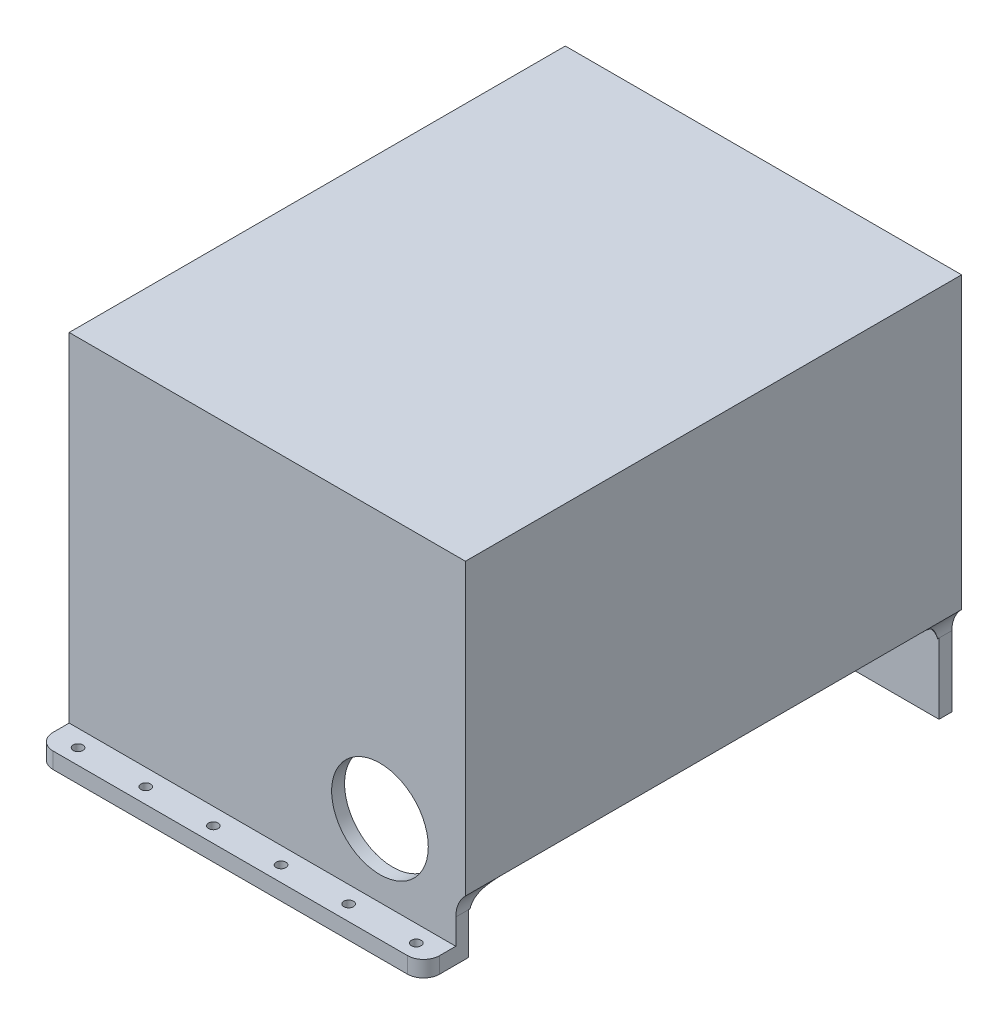
SolidWorks part; units mm, degrees
ref_plane "正面" through (0, 0, 0) normal (0, 0, 1) x (1, 0, 0)
ref_plane "平面" through (0, 0, 0) normal (0, 1, 0) x (1, 0, 0)
ref_plane "右側面" through (0, 0, 0) normal (1, 0, 0) x (0, 0, -1)
sketch "ｽｹｯﾁ1" plane through (0, 0, 0) normal (0, 1, 0) x (1, 0, 0)
  line L1 (0, 0) -> (120, 0)
  line L2 (0, 0) -> (0, 10)
  line L3 (0, 10) -> (120, 10)
  line L4 (120, 0) -> (120, 10)
  circle A0 centre (8, 4.759) radius 1.5
  circle A1 centre (29, 4.759) radius 1.5
  circle A2 centre (50, 4.759) radius 1.5
  circle A3 centre (71, 4.759) radius 1.5
  circle A4 centre (92, 4.759) radius 1.5
  circle A5 centre (113, 4.759) radius 1.5
  dimension "D2" = 3
  dimension "D3" = 3
  dimension "D4" = 3
  dimension "D5" = 3
  dimension "D9" = 3
  dimension "D11" = 3
  dimension "D12" = 21
  dimension "D1" = 10
  dimension "D6" = 21
  dimension "D7" = 21
  dimension "D8" = 21
  dimension "D10" = 21
  dimension "D13" = 8
extrude "ﾎﾞｽ - 押し出し1" add sketch "ｽｹｯﾁ1" along normal blind 5
sketch "ｽｹｯﾁ2" plane through (0, 0, 0) normal (0, -1, 0) x (-1, 0, 0)
  line L1 (0, 10) -> (-120, 10)
  line L2 (0, 10) -> (0, 14)
  line L3 (0, 14) -> (-120, 14)
  line L4 (-120, 10) -> (-120, 14)
  dimension "D1" = 120
  dimension "D2" = 4
extrude "ﾎﾞｽ - 押し出し2" add sketch "ｽｹｯﾁ2" against normal blind 110
sketch "ｽｹｯﾁ3" plane through (0, 0, -14) normal (0, 0, -1) x (-1, 0, 0)
  line L0 (0, 110) -> (0, 0) construction
  line L1 (-120, 110) -> (0, 110)
  line L2 (-120, 110) -> (-120, 106)
  line L3 (-120, 106) -> (0, 106)
  line L4 (0, 110) -> (0, 106)
  dimension "4" = 4
extrude "ﾎﾞｽ - 押し出し3" add sketch "ｽｹｯﾁ3" along normal blind 150
sketch "ｽｹｯﾁ4" plane through (0, 106, 0) normal (0, -1, 0) x (-1, 0, 0)
  line L0 (-120, 164) -> (-120, 14) construction
  line L1 (0, 164) -> (-120, 164)
  line L2 (0, 164) -> (0, 160)
  line L3 (0, 160) -> (-120, 160)
  line L4 (-120, 164) -> (-120, 160)
  dimension "D1" = 4
extrude "ﾎﾞｽ - 押し出し4" add sketch "ｽｹｯﾁ4" along normal blind 115
sketch "ｽｹｯﾁ5" plane through (120, 0, 0) normal (1, 0, 0) x (0, 0, -1)
  line L0 (164, 110) -> (164, -9) construction
  line L1 (10, 110) -> (164, 110)
  line L2 (10, 110) -> (10, 20)
  line L3 (10, 20) -> (164, 20)
  line L4 (164, 110) -> (164, 20)
  dimension "D1" = 90
extrude "ﾎﾞｽ - 押し出し5" add sketch "ｽｹｯﾁ5" along normal blind 3
sketch "ｽｹｯﾁ6" plane through (0, 0, 0) normal (-1, 0, 0) x (0, 0, 1)
  line L1 (-10, 110) -> (-80, 110)
  line L2 (-10, 110) -> (-10, 0)
  line L3 (-10, 0) -> (-80, 0)
  line L4 (-80, 110) -> (-80, 0)
  dimension "D1" = 70
extrude "ﾎﾞｽ - 押し出し6" add sketch "ｽｹｯﾁ6" against normal blind 4
sketch "ｽｹｯﾁ7" plane through (0, 0, 0) normal (-1, 0, 0) x (0, 0, 1)
  line L0 (-80, 106) -> (-80, 0) construction
  line L1 (-164, 110) -> (-80, 110)
  line L2 (-164, 110) -> (-164, 50)
  line L3 (-164, 50) -> (-80, 50)
  line L4 (-80, 110) -> (-80, 50)
  dimension "D1" = 60
extrude "ﾎﾞｽ - 押し出し7" add sketch "ｽｹｯﾁ7" against normal blind 4
fillet "ﾌｨﾚｯﾄ1" radius 10 1 edges at (120, 20, -12)
fillet "ﾌｨﾚｯﾄ2" radius 10 1 edges at (120, 20, -162)
fillet "ﾌｨﾚｯﾄ3" radius 10 2 edges at (121.5, 20, -14) (121.5, 20, -160)
fillet "ﾌｨﾚｯﾄ4" radius 5 2 edges at (2, 50, -160) (2, 50, -80)
sketch "ｽｹｯﾁ8" plane through (0, 0, 0) normal (-1, 0, 0) x (0, 0, 1)
  line L0 (-74.3681, 0) -> (-49.3681, 0)
  line L1 (-80, 0) -> (0, 0) construction
  line L2 (-49.3681, 0) -> (-49.3681, 18.4451)
  line L3 (-49.3681, 18.4451) -> (-74.3681, 18.4451)
  line L4 (-74.3681, 18.4451) -> (-74.3681, 0)
  circle A0 centre (-61.8681, 18.4451) radius 12.5
  line M6 (-80, 0) -> (0, 0)
  dimension "D1" = 25
extrude "ｶｯﾄ - 押し出し1" cut sketch "ｽｹｯﾁ8" against normal blind 4 contours L3 A0 | L3 A0 | A0 L4 L2 M6 region at (0, 4.7649, -61.8681) region at (0, 23.7503, -61.8681) region at (0, 13.14, -61.8681)
sketch "ｽｹｯﾁ9" plane through (0, 0, -10) normal (0, 0, 1) x (1, 0, 0)
  circle A0 centre (96.4724, 27.4796) radius 15
  dimension "D1" = 30
extrude "ｶｯﾄ - 押し出し2" cut sketch "ｽｹｯﾁ9" against normal blind 1000
fillet "ﾌｨﾚｯﾄ5" radius 5 2 edges at (0, 2.5, 0) (120, 2.5, 0)
